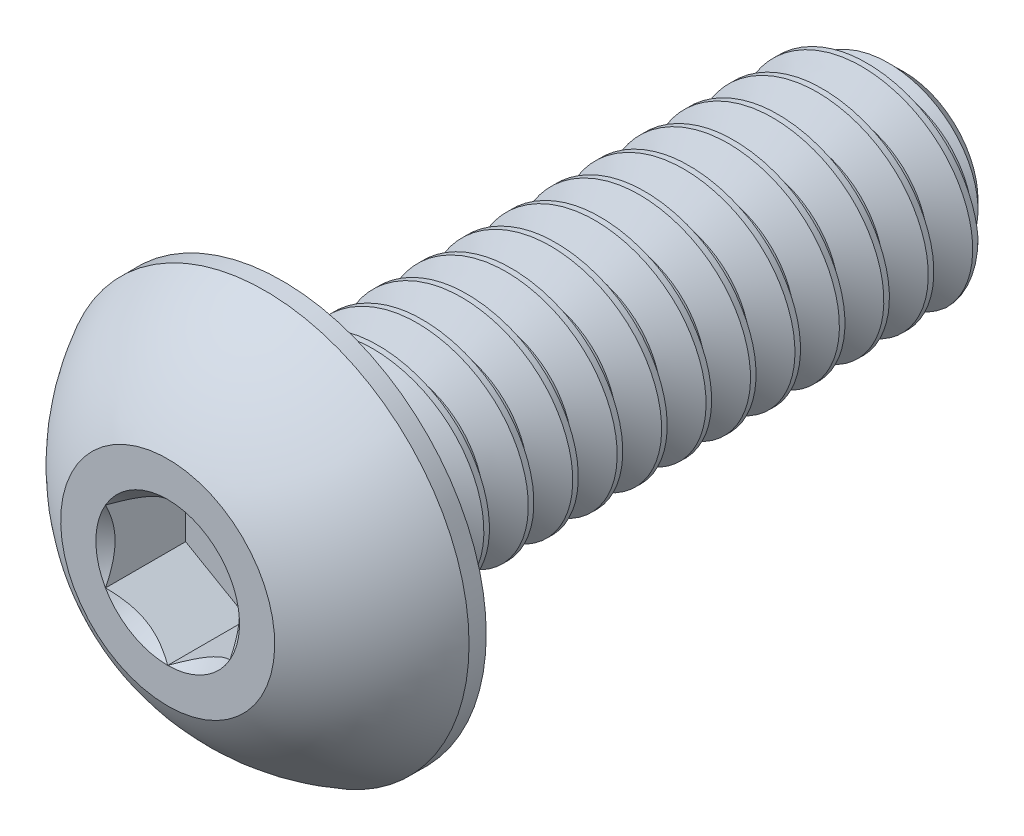
SolidWorks part; units mm, degrees
material "AISI 304"
ref_plane "Front" through (0, 0, 0) normal (0, 0, 1) x (1, 0, 0)
ref_plane "Top" through (0, 0, 0) normal (0, 1, 0) x (1, 0, 0)
ref_plane "Right" through (0, 0, 0) normal (1, 0, 0) x (0, 0, -1)
sketch "Sketch1" plane through (0, 0, 0) normal (1, 0, 0) x (0, 0, -1)
  line L2 (1.1684, 1.0922) -> (7.5184, 1.0922)
  line L3 (7.5184, 1.0922) -> (7.5184, 0)
  line L4 (7.5184, 0) -> (1.1684, 0)
  line L6 (0.9931, 2.0828) -> (1.1684, 2.0828) construction
  line L7 (7.5184, 1.0922) -> (7.5184, -1.0922) construction
  line L8 (0, 0) -> (1.1684, 0) construction
  line L9 (1.1684, 2.0828) -> (1.1684, -2.0828) construction
  line L11 (1.1684, 1.0922) -> (1.1684, 0)
  line L13 (0, 0.635) -> (0, -0.635) construction
  line L14 (0, 0.635) -> (0, 1.0922) construction
  arc A3 (0, 1.0922) -> (0.9931, 2.0828) centre (2.08, 0) cw construction
  dimension "D1" = 0.1753
revolve "Revolve1" add sketch "Sketch1" angle 360 mid plane about L4
sketch "Sketch3" plane through (0, 0, -7.5184) normal (0, 0, -1) x (-1, 0, 0)
  circle A0 centre (0, 0) radius 1.0922
curve "Helix/Spiral1" pitch 0.4536 height 6.8036 radius 1.0922 centre (0, 0, -7.5184) axis (0, 0, 1) start towards (0, 1, 0)
sketch "Sketch2" plane through (0, 0, 0) normal (1, 0, 0) x (0, 0, -1)
  line L0 (7.5184, 1.0922) -> (7.9153, 1.0922)
  line L1 (7.9153, 1.0922) -> (7.7452, 0.7976)
  line L2 (7.7452, 0.7976) -> (7.6885, 0.7976)
  line L3 (7.6885, 0.7976) -> (7.5184, 1.0922)
  line L4 (7.6034, 0.9449) -> (7.8302, 0.9449) construction
  dimension "D1" = 60
  dimension "D2" = 0.0567
  dimension "D3" = 0.2268
chamfer "Chamfer1" distance 0.3402 angle 45 1 edges at (0, 1.0922, -7.5184)
sweep "Cut-Sweep1" cut profiles "Sketch2" path "Helix/Spiral1" align with end faces yes
sketch "Sketch7" plane through (0, 0, 0) normal (1, 0, 0) x (0, 0, -1)
  line L6 (0.9931, 2.0828) -> (1.1684, 2.0828) construction
  line L8 (0, 0) -> (1.1684, 0) construction
  line L11 (1.1684, 2.0828) -> (1.1684, -2.0828) construction
  line L12 (0.9931, 2.0828) -> (1.1684, 2.0828)
  line L13 (0, 0) -> (1.1684, 0)
  line L14 (0, 0.635) -> (0, -0.635) construction
  line L15 (1.1684, 2.0828) -> (1.1684, 0)
  line L16 (0, 1.0922) -> (0, 0)
  arc A2 (0.9931, 2.0828) -> (0, 1.0922) centre (2.08, 0) ccw construction
  arc A3 (0.9931, 2.0828) -> (0, 1.0922) centre (2.08, 0) ccw
revolve "Revolve2" add sketch "Sketch7" angle 360 mid plane about L13
sketch "Sketch5" plane through (0, 0, 0) normal (0, 0, 1) x (1, 0, 0)
  line L1 (0.635, -0.3666) -> (0.635, 0.3666)
  line L2 (0.635, 0.3666) -> (0, 0.7332)
  line L3 (0, 0.7332) -> (-0.635, 0.3666)
  line L4 (-0.635, 0.3666) -> (-0.635, -0.3666)
  line L5 (-0.635, -0.3666) -> (0, -0.7332)
  line L6 (0, -0.7332) -> (0.635, -0.3666)
  circle A0 centre (0, 0) radius 0.635 construction
extrude "Cut-Extrude2" cut sketch "Sketch5" against normal blind 0.8179
sketch "Sketch6" plane through (0, 0, 0) normal (0, 0, 1) x (1, 0, 0)
  circle A0 centre (0, 0) radius 0.7332
extrude "Cut-Extrude3" cut sketch "Sketch6" against normal blind 0.8179 draft 45
sketch "Sketch9" [suppressed] plane through (0, 0, -1.1684) normal (0, 0, 1) x (1, 0, 0)
  circle A2 centre (0, 0) radius 1.0922
extrude "Boss-Extrude2" [suppressed] add sketch "Sketch9" against normal offset from surface (6.35 mm away) 31.75 up to face at (0, 0.752, -7.5184)
sketch "Sketch10" plane through (0, 0, 0) normal (1, 0, 0) x (0, 0, -1)
  line L0 (7.5184, 1.0922) -> (7.5184, -1.0922) construction
  point P0 (6.838, -1.0922)
  dimension "D1" = 0.6804
equation "\"D3@Helix/Spiral1\" = \"Lg@Sketch1\" + \"D4@Helix/Spiral1\""
equation "\"D2@Sketch2\" = \"D4@Helix/Spiral1\" * .125"
equation "\"D3@Sketch2\" = \"D4@Helix/Spiral1\" * .5"
equation "\"D1@Chamfer1\" = \"D4@Helix/Spiral1\" * .75"
equation "\"D1@Cut-Extrude2\" = \"Head Ht@Sketch1\" * .7"
equation "\"D1@Sketch1\" = \"Head Ht@Sketch1\" * .15"
equation "\"D1@Sketch10\" = \"D4@Helix/Spiral1\" * 1.5"
equation "\"D1@Cut-Extrude3\" = \"D1@Cut-Extrude2\""
